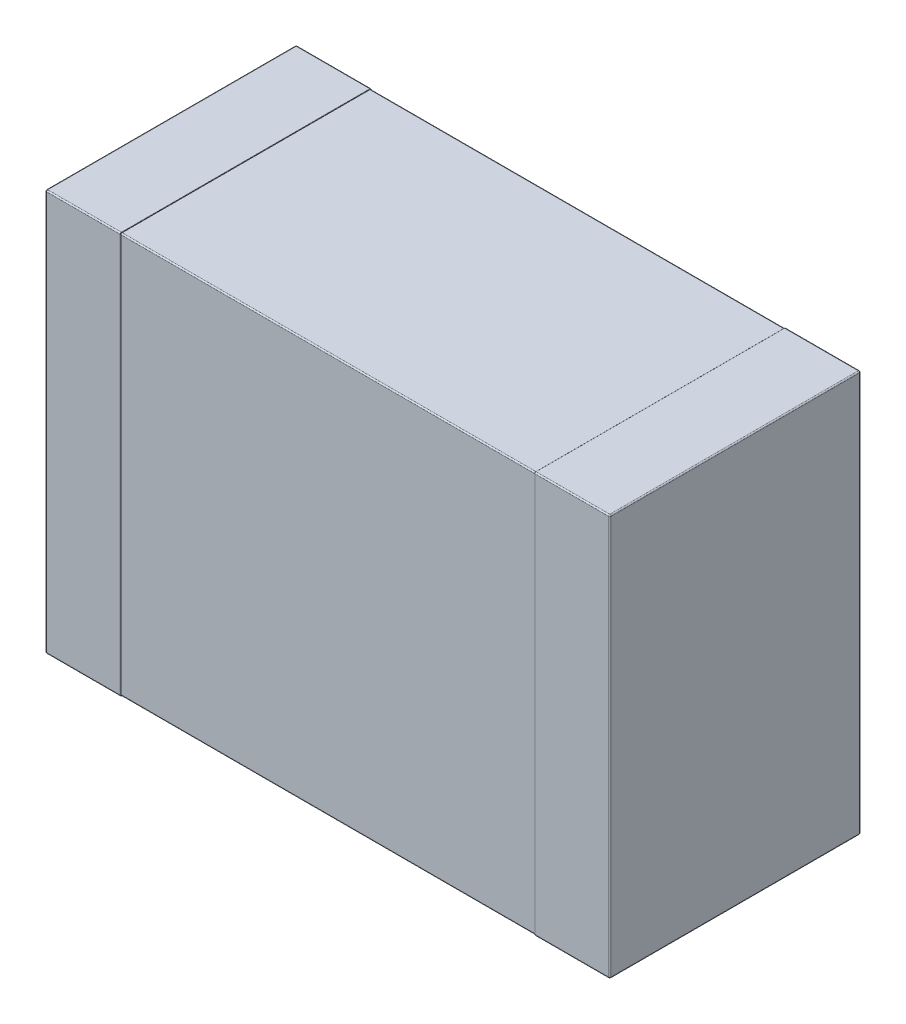
SolidWorks part; units mm, degrees
ref_plane "Top Plane" through (0, 0, 0) normal (0, 0, 1) x (1, 0, 0)
ref_plane "Front Plane" through (0, 0, 0) normal (0, 1, 0) x (1, 0, 0)
ref_plane "Side Plane" through (0, 0, 0) normal (1, 0, 0) x (0, 0, -1)
sketch "Sketch1" plane through (0, 0, 0) normal (0, 0, 1) x (1, 0, 0)
  line L1 (-2.25, 1.6) -> (2.25, 1.6)
  line L2 (-2.25, 1.6) -> (-2.25, -1.6)
  line L3 (-2.25, -1.6) -> (2.25, -1.6)
  line L4 (2.25, 1.6) -> (2.25, -1.6)
  dimension "D1" = 4.5
  dimension "D2" = 2.25
  dimension "D3" = 3.2
  dimension "D4" = 1.6
extrude "All body" add sketch "Sketch1" along normal blind 2
sketch "Sketch2" plane through (0, 0, 0) normal (1, 0, 0) x (0, 0, -1)
  line L14 (-0.003, 1.597) -> (-1.997, 1.597)
  line L15 (-0.003, -1.597) -> (-0.003, 1.597)
  line L16 (-1.997, -1.597) -> (-0.003, -1.597)
  line L17 (-1.997, 1.597) -> (-1.997, -1.597)
  line L18 (-0.003, 1.597) -> (-1.997, 1.597)
  line L19 (-0.003, -1.597) -> (-0.003, 1.597)
  line L20 (-1.997, -1.597) -> (-0.003, -1.597)
  line L21 (-1.997, 1.597) -> (-1.997, -1.597)
  dimension "D1" = 0.003
extrude "Cut out the body for pin" cut sketch "Sketch2" against normal blind 1.65 and the other way blind 1.65 flip side to cut
fillet "Body fillet" radius 0.01 4 edges at (0, 1.597, 0.003) (0, 1.597, 1.997) (0, -1.597, 0.003) (0, -1.597, 1.997)
fillet "Pin fillet a" radius 0.01 16 edges at (2.25, -1.6, 1) (2.25, 0, 2) (2.25, 1.6, 1) (2.25, 0, 0) (-2.25, 1.6, 1) (-2.25, 0, 2) (-2.25, -1.6, 1) (-2.25, 0, 0) (1.95, 1.6, 2) (1.95, -1.6, 2) (1.95, -1.6, 0) (1.95, 1.6, 0) (-1.95, 1.6, 0) (-1.95, -1.6, 0) (-1.95, 1.6, 2) (-1.95, -1.6, 2)
fillet "Pin fillet b" radius 0.003 16 edges at (1.65, -1.5971, 1.9971) (1.65, -1.6, 1) (1.65, -1.5971, 0.0029) (1.65, 0, 0) (1.65, 1.5971, 0.0029) (1.65, 1.6, 1) (1.65, 1.5971, 1.9971) (-1.65, -1.5971, 1.9971) (-1.65, -1.6, 1) (-1.65, -1.5971, 0.0029) (-1.65, 0, 0) (-1.65, 1.5971, 0.0029) (-1.65, 1.6, 1) (-1.65, 1.5971, 1.9971) (1.65, 0, 2) (-1.65, 0, 2)
